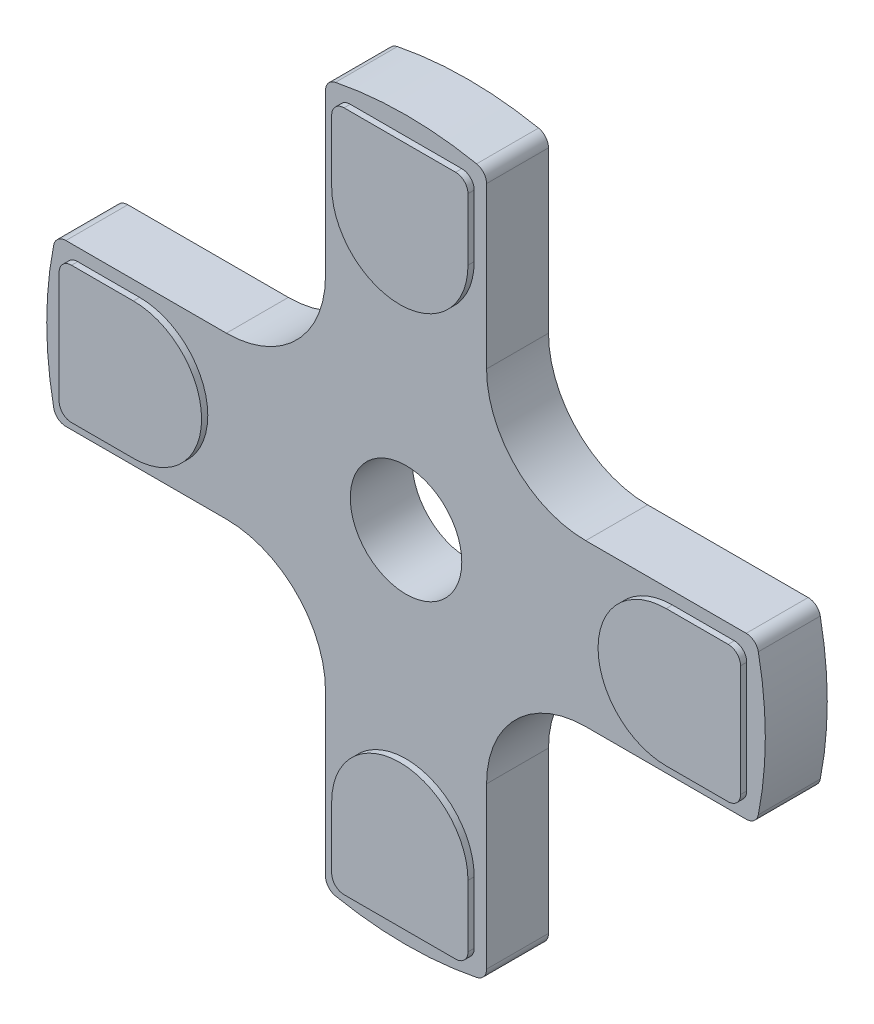
SolidWorks part; units mm, degrees
material "ASTM A36 Steel"
ref_plane "Front Plane" through (0, 0, 0) normal (0, 0, 1) x (1, 0, 0)
ref_plane "Top Plane" through (0, 0, 0) normal (0, 1, 0) x (1, 0, 0)
ref_plane "Right Plane" through (0, 0, 0) normal (1, 0, 0) x (0, 0, -1)
ref_axis "Axis1" through (0, 0, -0.0546) along (0, 0, 1)
sketch "Sketch1" plane through (0, 0, 0) normal (0, 0, 1) x (1, 0, 0)
  line L1 (0.0656, 0.0656) -> (0.5098, 0.5098) construction
  line L3 (0, 1.2013) -> (0, 1.7243) construction
  line L11 (3.2767, -0.1016) -> (2.3253, -0.1016) construction
  line L12 (3.2767, -0.1016) -> (3.2767, 0.1016) construction
  line L18 (3.2767, 0.1016) -> (2.3253, 0.1016) construction
  line L23 (-0.1422, 1.2917) -> (0.5478, 0.6017) construction
  circle A0 centre (0, 0) radius 1.4732
  circle A1 centre (0, 0) radius 0.2286
  circle A2 centre (0.5747, 0.5747) radius 0.4318 construction
  circle A7 centre (0.5747, 0.5747) radius 0.0381 construction
  point P45 (3.2767, 0)
  dimension "D5" = 0.4572
  dimension "D10" = 0.0762
  dimension "D6" = 0.8636
  dimension "D2" = 2.9464
  dimension "D3" = 0.8128
  dimension "D4" = 45
  dimension "D14" = 0.2032
  dimension "D15" = 2.3253
  dimension "D16" = 0.9514
  dimension "D18" = 45
extrude "Boss-Extrude1" add sketch "Sketch1" along normal blind 0.254
sketch "Sketch11" plane through (0, 0, 0) normal (0, 0, 1) x (1, 0, 0)
  line L0 (2.5435, 0.3302) -> (0.7366, 0.3302)
  line L1 (0.3302, 0.7366) -> (0.3302, 2.5435)
  line L2 (0.3302, 2.5435) -> (2.5435, 0.3302)
  line L3 (0.0656, 0.0656) -> (0.5098, 0.5098) construction
  arc A0 (0.7366, 0.3302) -> (0.3302, 0.7366) centre (0.7366, 0.7366) cw
  dimension "D2" = 0.4064
  dimension "D1" = 0.3302
  dimension "D3" = 2.032
extrude "Cut-Extrude3" cut sketch "Sketch11" along normal through all
fillet "Fillet1" radius 0.0508 2 edges at (1.4357, 0.3302, 0.127) (0.3302, 1.4357, 0.127)
pattern_circular "CirPattern2" count 4 over 360 about axis through (0, 0, -0.0546) along (0, 0, 1) of "Cut-Extrude3", "Fillet1"
sketch "Sketch2" plane through (0, 0, 0.254) normal (0, 0, 1) x (1, 0, 0)
  line L0 (0.6177, 0.4552) -> (0.9718, 0.1012) construction
  line L1 (1.0922, 0.2794) -> (1.3462, 0.2794)
  line L2 (1.397, 0.2286) -> (1.397, -0.2286)
  line L3 (1.0922, -0.2794) -> (1.3462, -0.2794)
  line L5 (0.5747, 0.5747) -> (0.354, 0.354) construction
  line L6 (1.0483, 0.1777) -> (0.6942, 0.5317) construction
  line L8 (1.0483, 0.1777) -> (0.9718, 0.1012) construction
  line L9 (1.01, 0.1394) -> (0.5747, 0.5747) construction
  arc A1 (1.3462, 0.2794) -> (1.397, 0.2286) centre (1.3462, 0.2286) cw
  arc A3 (0.6942, 0.5317) -> (0.6177, 0.4552) centre (0.5747, 0.5747) ccw construction
  arc A5 (1.3462, -0.2794) -> (1.397, -0.2286) centre (1.3462, -0.2286) ccw
  arc A6 (1.0922, 0.2794) -> (1.0922, -0.2794) centre (1.0922, 0) ccw
  dimension "D6" = 0.127
  dimension "D8" = 0.0508
  dimension "D9" = 1.397
  dimension "D3" = 0.3048
  dimension "D5" = 1.0922
  dimension "D7" = 0.5588
extrude "Boss-Extrude2" add sketch "Sketch2" along normal blind 0.0254
sketch "Sketch5" plane through (0, 0, 0) normal (0, 0, -1) x (-1, 0, 0)
  line L0 (-1.397, 0.2286) -> (-1.397, -0.2286) construction
  line L1 (-1.0922, -0.2794) -> (-1.3462, -0.2794) construction
  line L2 (-1.0922, 0.2794) -> (-1.3462, 0.2794) construction
  line L5 (-1.397, 0.2286) -> (-1.397, -0.2286)
  line L6 (-1.0922, -0.2794) -> (-1.3462, -0.2794)
  line L7 (-1.0922, 0.2794) -> (-1.3462, 0.2794)
  arc A0 (-1.397, -0.2286) -> (-1.3462, -0.2794) centre (-1.3462, -0.2286) ccw construction
  arc A1 (-1.0922, -0.2794) -> (-1.0922, 0.2794) centre (-1.0922, 0) ccw construction
  arc A2 (-1.3462, 0.2794) -> (-1.397, 0.2286) centre (-1.3462, 0.2286) ccw construction
  arc A7 (-1.397, -0.2286) -> (-1.3462, -0.2794) centre (-1.3462, -0.2286) ccw
  arc A8 (-1.0922, -0.2794) -> (-1.0922, 0.2794) centre (-1.0922, 0) ccw
  arc A9 (-1.3462, 0.2794) -> (-1.397, 0.2286) centre (-1.3462, 0.2286) ccw
extrude "Boss-Extrude4" add sketch "Sketch5" along normal blind 0.0178
pattern_circular "CirPattern1" count 4 over 360 about axis through (0, 0, -0.0546) along (0, 0, 1) of "Boss-Extrude2", "Boss-Extrude4"
